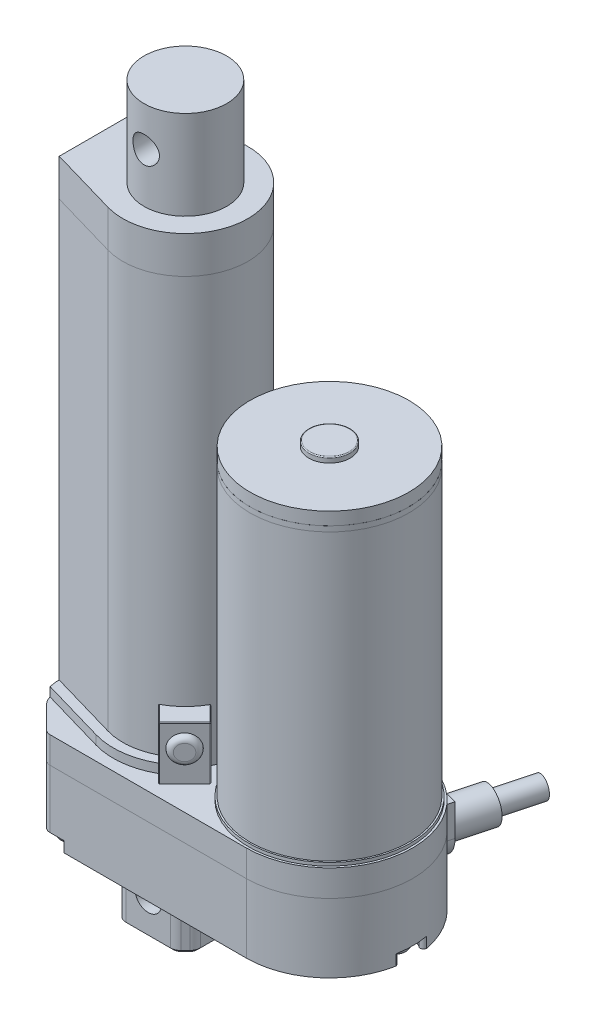
SolidWorks part; units mm, degrees
note: The reader was unsure of these and kept them because the rebuilt part matched: shared geometry of "Sketch1<3>", "Sketch41<11>", "Sketch41<12>", "Sketch45<3>".
ref_plane "Front Plane" through (0, 0, 0) normal (0, 0, 1) x (1, 0, 0)
ref_plane "Top Plane" through (0, 0, 0) normal (0, 1, 0) x (1, 0, 0)
ref_plane "Right Plane" through (0, 0, 0) normal (1, 0, 0) x (0, 0, -1)
sketch "Sketch1" plane through (0, 0, 0) normal (0, 1, 0) x (1, 0, 0)
  line L0 (0, 32.639) -> (7.239, 39.878)
  line L1 (7.239, 0) -> (55.118, 0)
  line L2 (0, 7.239) -> (0, 32.639)
  line L3 (7.239, 39.878) -> (55.118, 39.878)
  line L4 (7.239, 0) -> (0, 7.239)
  arc A0 (55.118, 0) -> (55.118, 39.878) centre (55.118, 19.939) ccw
  point P0 (0, 0)
  point P2 (0, 39.878)
  dimension "D1" = 55.118
  dimension "D2" = 39.878
extrude "Boss-Extrude1" add sketch "Sketch1" along normal blind 6.35
sketch "Sketch6" plane through (0, 6.35, 0) normal (0, 1, 0) x (1, 0, 0)
  circle A0 centre (55.118, 19.939) radius 19.431
extrude "Boss-Extrude4" add sketch "Sketch6" along normal blind 0.762 separate body contours A0
sketch "Sketch7" plane through (0, 7.112, 0) normal (0, 1, 0) x (1, 0, 0)
  circle A0 centre (55.118, 19.939) radius 19.05
  dimension "D1" = 38.1
extrude "Boss-Extrude5" add sketch "Sketch7" along normal blind 68.326 separate body
sketch "Sketch8" plane through (0, 75.438, 0) normal (0, 1, 0) x (1, 0, 0)
  circle A0 centre (55.118, 19.939) radius 4.953
  dimension "D1" = 9.906
fillet "Fillet6" radius 5.08 2 edges at (0, 3.175, -7.239) (0, 3.175, -32.639)
fillet "Fillet7" radius 1.905 2 edges at (7.239, 3.175, -39.878) (7.239, 3.175, 0)
sketch "Sketch15" plane through (0, 6.35, 0) normal (0, 1, 0) x (1, 0, 0)
  line L0 (35.5603, 29.0153) -> (35.5603, 29.0265)
  line L2 (0, 30.5348) -> (0, 9.3432) construction
  line L3 (0, 19.939) -> (0, 10.2869)
  line L4 (0, 19.939) -> (0, 29.591)
  line L5 (0, 10.2869) -> (16.412, 5.5423)
  line L7 (35.5603, 10.8628) -> (35.5603, 10.8515)
  line L10 (0, 29.591) -> (16.4119, 34.3357)
  arc A0 (16.412, 5.5423) -> (16.4119, 34.3357) centre (20.574, 19.939) ccw
ref_plane "Plane4" through (13.8375, 0, -51.6424) normal (0.2588, 0, -0.9659) x (0, -1, 0)
ref_plane "Plane5" through (12.5227, 0, -46.7355) normal (0.2588, 0, -0.9659) x (0, -1, 0)
sketch "Sketch23" plane through (12.5227, 0, -46.7355) normal (0.2588, 0, -0.9659) x (0, -1, 0)
  line L0 (-6.35, -67.5103) -> (-6.35, -28.6483) construction
  line L1 (-2.032, -53.8839) -> (5.588, -53.8839)
  line L2 (-2.032, -53.8839) -> (-2.032, -42.4539)
  line L3 (-2.032, -42.4539) -> (5.588, -42.4539)
  arc A0 (5.588, -53.8839) -> (5.588, -42.4539) centre (5.588, -48.1689) ccw
  dimension "D1" = 11.43
  dimension "D2" = 7.62
  dimension "D3" = 4.318
extrude "Boss-Extrude15" add sketch "Sketch23" along normal blind 6.35
sketch "Sketch24" plane through (14.1662, 0, -52.8692) normal (0.2588, 0, -0.9659) x (-0.9659, 0, -0.2588)
  circle A0 centre (-48.1689, -5.588) radius 4.064
  dimension "D1" = 8.128
extrude "Boss-Extrude16" add sketch "Sketch24" along normal blind 10.16
sketch "Sketch25" plane through (16.7959, 0, -62.683) normal (0.2588, 0, -0.9659) x (-0.9659, 0, -0.2588)
  circle A0 centre (-48.1689, -5.588) radius 2.54
  dimension "D1" = 5.08
extrude "Boss-Extrude17" add sketch "Sketch25" along normal blind 10.16
extrude "Boss-Extrude19" add sketch "Sketch1<3>" against normal blind 16.51 separate body
sketch "Sketch1<3>" plane through (0, 0, 0) normal (0, 1, 0) x (1, 0, 0) same geometry as "Sketch1"
fillet "Fillet13" radius 1.905 2 edges at (7.239, -8.255, 0) (7.239, -8.255, -39.878)
fillet "Fillet14" radius 5.08 2 edges at (0, -8.255, -32.639) (0, -8.255, -7.239)
sketch "Sketch26" plane through (0, -16.51, 0) normal (0, -1, 0) x (-1, 0, 0)
  line L4 (-20.574, 28.829) -> (-11.684, 28.829)
  line L5 (-20.574, 28.829) -> (-29.464, 28.829)
  line L6 (-11.684, 28.829) -> (-11.684, 11.049)
  line L7 (-11.684, 11.049) -> (-29.464, 11.049)
  line L8 (-29.464, 11.049) -> (-29.464, 28.829)
extrude "Boss-Extrude20" add sketch "Sketch26" along normal blind 18.796 separate body
chamfer "Chamfer1" distance 2.54 angle 45 4 edges at (29.464, -25.908, -28.829) (29.464, -25.908, -11.049) (11.684, -25.908, -11.049) (11.684, -25.908, -28.829)
fillet "Fillet15" radius 2.54 8 edges at (11.684, -25.908, -13.589) (14.224, -25.908, -11.049) (26.924, -25.908, -11.049) (29.464, -25.908, -13.589) (29.464, -25.908, -26.289) (26.924, -25.908, -28.829) (11.684, -25.908, -26.289) (14.224, -25.908, -28.829)
chamfer "Chamfer2" distance 0.762 angle 45 16 edges at (14.3041, -35.306, -11.2423) (20.574, -35.306, -11.049) (26.8439, -35.306, -11.2423) (28.194, -35.306, -12.319) (29.2707, -35.306, -13.6691) (29.464, -35.306, -19.939) (29.2707, -35.306, -26.2089) (28.194, -35.306, -27.559) (26.8439, -35.306, -28.6357) (20.574, -35.306, -28.829) (14.3041, -35.306, -28.6357) (12.954, -35.306, -27.559) (11.8773, -35.306, -26.2089) (11.684, -35.306, -19.939) (11.8773, -35.306, -13.6691) (12.954, -35.306, -12.319)
sketch "Sketch27" plane through (0, 0, -11.049) normal (0, 0, 1) x (1, 0, 0)
  circle A0 centre (20.574, -26.67) radius 3.175
extrude "Cut-Extrude3" cut sketch "Sketch27" against normal blind 19.05
sketch "Sketch28" plane through (0, 75.438, 0) normal (0, 1, 0) x (1, 0, 0)
  circle A0 centre (55.118, 19.939) radius 19.05
extrude "Boss-Extrude22" add sketch "Sketch28" along normal blind 1.27 separate body
sketch "Sketch29" plane through (0, 76.708, 0) normal (0, 1, 0) x (1, 0, 0)
  circle A0 centre (55.118, 19.939) radius 19.05
extrude "Boss-Extrude24" add sketch "Sketch29" along normal blind 3.048 separate body contours A0
extrude "Boss-Extrude25" add sketch "Sketch8" along normal blind 1.27 from surface at 4.318 contours A0 starting at face at (55.118, 79.756, -0.889)
fillet "Fillet16" radius 0.2286 1 edges at (55.118, 81.026, -14.986)
extrude "Boss-Extrude26" add sketch "Sketch15" along normal blind 101.981 separate body contours L5 A0 L10 L4 L3
sketch "Sketch32" plane through (0, 108.331, 0) normal (0, 1, 0) x (1, 0, 0)
  line L0 (0, 10.2869) -> (0, 29.591)
  line L1 (0, 29.591) -> (16.4119, 34.3357)
  line L2 (0, 10.2869) -> (16.412, 5.5423)
  arc A0 (16.412, 5.5423) -> (16.4119, 34.3357) centre (20.574, 19.939) ccw
extrude "Boss-Extrude27" add sketch "Sketch32" along normal blind 8.89 separate body
sketch "Sketch33" plane through (0, 117.221, 0) normal (0, 1, 0) x (1, 0, 0)
  circle A0 centre (20.574, 19.939) radius 9.906
extrude "Boss-Extrude28" add sketch "Sketch33" along normal blind 21.336
sketch3d "3DSketch1" plane through (0, 0, 0) normal (0, 0, 1) x (1, 0, 0)
sketch "Sketch41" plane through (0, 6.35, 0) normal (0, 1, 0) x (1, 0, 0)
  line L0 (16.4119, 34.3357) -> (0, 29.591)
  line L1 (37.5429, 9.0662) -> (33.7712, 12.8379)
  line L2 (0.2737, 32.0497) -> (15.777, 36.5318)
  line L3 (37.5429, 9.0662) -> (31.2567, 2.78)
  line L4 (0, 29.591) -> (0, 30.5348)
  line L5 (0, 30.5348) -> (0.2737, 32.0497)
  line L6 (-0.6349, 31.7871) -> (15.777, 36.5318) construction
  line L7 (0, 19.9389) -> (7.9017, 19.9389)
  line L8 (31.2567, 2.78) -> (27.426, 6.6107)
  line L9 (0, 10.2869) -> (0, 29.591) construction
  line L10 (0, 10.2869) -> (0, 9.3431)
  line L12 (37.5429, 30.8116) -> (33.7712, 27.0399)
  line L13 (37.5429, 30.8116) -> (31.2567, 37.0978)
  line L14 (31.2567, 37.0978) -> (27.426, 33.2671)
  line L15 (0, 9.3431) -> (0.2737, 7.8281)
  line L16 (0.2737, 7.8281) -> (15.777, 3.3461)
  line L17 (16.4119, 5.5422) -> (0, 10.2869)
  line L18 (-0.6349, 8.0908) -> (15.7771, 3.3462) construction
  line L19 (27.426, 33.2671) -> (29.1122, 34.9533)
  line L20 (0, 29.591) -> (16.4119, 34.3357) construction
  line L21 (0, 10.2869) -> (16.412, 5.5423) construction
  arc A0 (16.4119, 34.3357) -> (33.7712, 27.0399) centre (20.574, 19.939) cw
  arc A1 (15.777, 36.5318) -> (29.1122, 34.9533) centre (20.574, 19.939) cw
  arc A2 (16.4119, 34.3357) -> (16.412, 5.5423) centre (20.574, 19.939) cw construction
  arc A3 (15.777, 36.5318) -> (15.7771, 3.3462) centre (20.574, 19.939) cw construction
  arc A4 (16.4119, 34.3357) -> (27.426, 33.2671) centre (20.574, 19.939) cw
  arc A5 (15.777, 3.3461) -> (29.1122, 4.9245) centre (20.574, 19.9389) ccw
  arc A6 (16.4119, 5.5422) -> (33.7712, 12.8379) centre (20.574, 19.9389) ccw
  line M5 (0, 30.5348) -> (0, 9.3432)
  arc M6 (0, 9.3432) -> (1.4879, 5.7511) centre (5.08, 9.3432) ccw
extrude "Boss-Extrude30" add sketch "Sketch41" along normal blind 2.159 separate body contours A1 L2 L5 L0 A0 L14 M5
extrude "Boss-Extrude31" add sketch "Sketch41<11>" along normal blind 2.159 separate body contours A6 L17 L15 L16 A5 L8 M5 M6
sketch "Sketch41<11>" plane through (0, 6.35, 0) normal (0, 1, 0) x (1, 0, 0) same geometry as "Sketch41"
extrude "Boss-Extrude33" add sketch "Sketch41<12>" along normal blind 12.7 separate body contours L14 A0 L12 L13 | A6 L8 L3 L1
sketch "Sketch41<12>" plane through (0, 6.35, 0) normal (0, 1, 0) x (1, 0, 0) same geometry as "Sketch41"
fillet "Fillet17" radius 0.2286 5 edges at (35.657, 19.05, -28.9258) (29.3413, 19.05, -35.1825) (34.3998, 19.05, -33.9547) (37.5429, 12.7, -30.8116) (31.2567, 12.7, -37.0978)
fillet "Fillet18" radius 0.2286 5 edges at (35.657, 19.05, -10.9521) (29.3413, 19.05, -4.6954) (37.5429, 12.7, -9.0662) (34.3998, 19.05, -5.9231) (31.2567, 12.7, -2.78)
sketch "Sketch43" plane through (34.1773, 0, -34.1773) normal (0.7071, 0, -0.7071) x (-0.7071, 0, -0.7071)
  circle A0 centre (-0.3147, 13.7414) radius 3.175
extrude "Boss-Extrude34" add sketch "Sketch43" along normal blind 1.27 separate body
fillet "Fillet19" radius 1.27 1 edges at (33.0527, 13.7414, -37.0978)
sketch "Sketch44" plane through (14.2383, 0, 14.2383) normal (0.7071, 0, 0.7071) x (0.7071, 0, -0.7071)
  circle A0 centre (28.5126, 13.7414) radius 3.175
extrude "Boss-Extrude35" add sketch "Sketch44" along normal blind 1.27 separate body
fillet "Fillet20" radius 1.27 1 edges at (37.5429, 13.7414, -7.2702)
sketch "Sketch45" plane through (0, -16.51, 0) normal (0, -1, 0) x (1, 0, 0)
  line L0 (4.0845, -36.7235) -> (6.681, -39.32)
  line L2 (6.681, -39.32) -> (1.4879, -34.1269) construction
  line L4 (55.118, -39.878) -> (8.0281, -39.878) construction
  line L5 (11.3938, -39.878) -> (8.0281, -39.878)
  line L6 (11.3938, 0) -> (8.0281, 0)
  line L7 (4.0845, -3.1545) -> (6.681, -0.558)
  arc A0 (11.2821, -38.9146) -> (11.3938, -39.878) centre (11.8197, -39.3405) ccw
  arc A1 (11.2821, -38.9146) -> (5.0443, -35.9783) centre (8.8543, -35.9783) ccw
  arc A2 (11.2821, -0.9634) -> (11.3938, 0) centre (11.8197, -0.5375) cw
  arc A3 (5.0443, -35.9783) -> (4.0845, -36.7235) centre (4.1918, -35.871) cw
  arc A4 (5.0443, -3.8997) -> (4.0845, -3.1545) centre (4.1918, -4.007) ccw
  arc A5 (11.2821, -0.9634) -> (5.0443, -3.8997) centre (8.8543, -3.8997) cw
  arc A6 (55.118, -39.878) -> (55.118, 0) centre (55.118, -19.939) ccw construction
  arc A7 (73.6621, -16.9922) -> (73.6621, -22.8858) centre (71.247, -19.939) ccw
  arc A8 (73.6621, -22.8858) -> (74.7121, -23.6317) centre (73.8141, -23.7837) cw
  arc A9 (73.6621, -16.9922) -> (74.7121, -16.2463) centre (73.8141, -16.0943) ccw
  arc A10 (8.0281, -39.878) -> (6.681, -39.32) centre (8.0281, -37.973) cw
  arc A11 (8.0281, 0) -> (6.681, -0.558) centre (8.0281, -1.905) ccw
  arc A12 (74.7121, -23.6317) -> (74.7121, -16.2463) centre (55.118, -19.939) ccw
  line M8 (1.4879, -34.1269) -> (6.681, -39.32)
  arc M9 (6.681, -39.32) -> (8.0281, -39.878) centre (8.0281, -37.973) ccw
  line M10 (8.0281, -39.878) -> (55.118, -39.878)
  line M12 (55.118, 0) -> (8.0281, 0)
  arc M13 (8.0281, 0) -> (6.681, -0.558) centre (8.0281, -1.905) ccw
  line M14 (6.681, -0.558) -> (1.4879, -5.7511)
extrude "Cut-Extrude5" cut sketch "Sketch45" against normal blind 2.54 contours A1 A3 A0 M8 M9 M10 | A5 A2 A4 M12 M13 M14
extrude "Cut-Extrude6" cut sketch "Sketch45<3>" against normal blind 2.54
sketch "Sketch45<3>" plane through (0, -16.51, 0) normal (0, -1, 0) x (1, 0, 0) same geometry as "Sketch45"
sketch "Sketch47" plane through (0, -13.97, 0) normal (0, -1, 0) x (-1, 0, 0)
  circle A0 centre (-8.8543, 35.9783) radius 2.54
  circle A1 centre (-8.8543, 3.8997) radius 2.54
  circle A2 centre (-71.247, 19.939) radius 2.54
extrude "Boss-Extrude36" add sketch "Sketch47" along normal blind 2.54 separate body
fillet "Fillet22" radius 1.524 1 edges at (8.8543, -16.51, -38.5183)
fillet "Fillet23" radius 1.524 1 edges at (8.8543, -16.51, -6.4397)
sketch "Sketch48" plane through (0, 0, 0) normal (-1, 0, 0) x (0, 0, 1)
  circle A0 centre (-19.939, 12.7) radius 3.81
extrude "Boss-Extrude37" add sketch "Sketch48" along normal blind 1.524
fillet "Fillet24" radius 1.524 1 edges at (-1.524, 12.7, -16.129)
fillet "Fillet25" radius 1.524 1 edges at (71.247, -16.51, -22.479)
sketch "Sketch49" plane through (0, 0, 0) normal (-1, 0, 0) x (0, 0, 1)
  line L0 (-19.9389, 108.331) -> (-19.9389, 103.378) construction
  line L1 (-29.591, 108.331) -> (-10.2869, 108.331) construction
  line L2 (-30.5348, 6.35) -> (-9.3432, 6.35) construction
  circle A0 centre (-19.9389, 103.378) radius 3.81
  dimension "Flat Head Screw" = 97.028
extrude "Cut-Extrude7" cut sketch "Sketch49" against normal blind 2.54
sketch "Sketch50" plane through (2.54, 0, 0) normal (-1, 0, 0) x (0, 0, 1)
  circle A0 centre (-19.9389, 103.378) radius 3.556
extrude "Boss-Extrude39" add sketch "Sketch50" along normal blind 2.54 contours A0
sketch "Sketch52" plane through (0, 0, -11.049) normal (0, 0, 1) x (1, 0, 0)
  circle A0 centre (20.574, 129.032) radius 3.175
  circle A1 centre (20.574, -26.67) radius 3.175 construction
  dimension "Hole to Hole" = 155.702
extrude "Cut-Extrude11" cut sketch "Sketch52" against normal through all both and the other way through all
equation "\"Stroke\"= 2"
equation "\"D1@Boss-Extrude26\"= \"Stroke\" + 2.015"
equation "\"Flat Head Screw@Sketch49\"= \"Stroke\" + 1.82"
equation "\"Hole to Hole@Sketch52\"= \"Stroke\" + 4.13"
